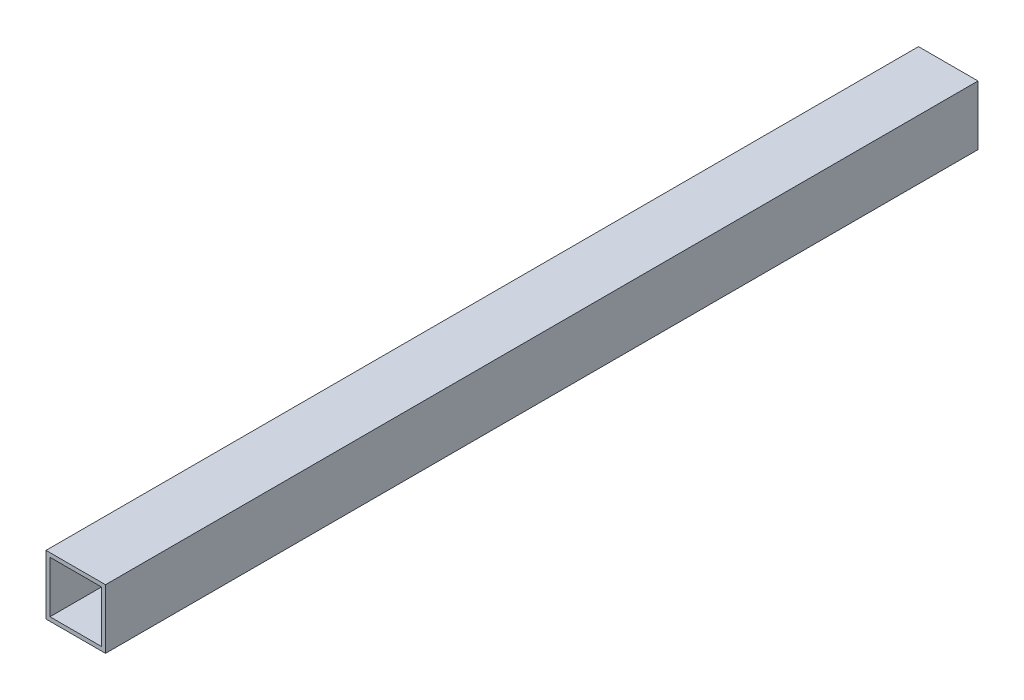
SolidWorks part; units mm, degrees
ref_plane "Front Plane" through (0, 0, 0) normal (0, 0, 1) x (1, 0, 0)
ref_plane "Top Plane" through (0, 0, 0) normal (0, 1, 0) x (1, 0, 0)
ref_plane "Right Plane" through (0, 0, 0) normal (1, 0, 0) x (0, 0, -1)
sketch "Esboço1" plane through (0, 0, 0) normal (0, 0, 1) x (1, 0, 0)
  line L1 (-4.3448, 102.2122) -> (25.6552, 102.2122)
  line L2 (-4.3448, 102.2122) -> (-4.3448, 72.2122)
  line L3 (-4.3448, 72.2122) -> (25.6552, 72.2122)
  line L4 (25.6552, 102.2122) -> (25.6552, 72.2122)
  dimension "D1" = 30
  dimension "D2" = 30
extrude "Ressalto-extrusão1" add sketch "Esboço1" along normal blind 440
shell "Casca1" thickness 2 removed face at (10.6552, 87.2122, 440) removed face at (10.6552, 87.2122, 0)
